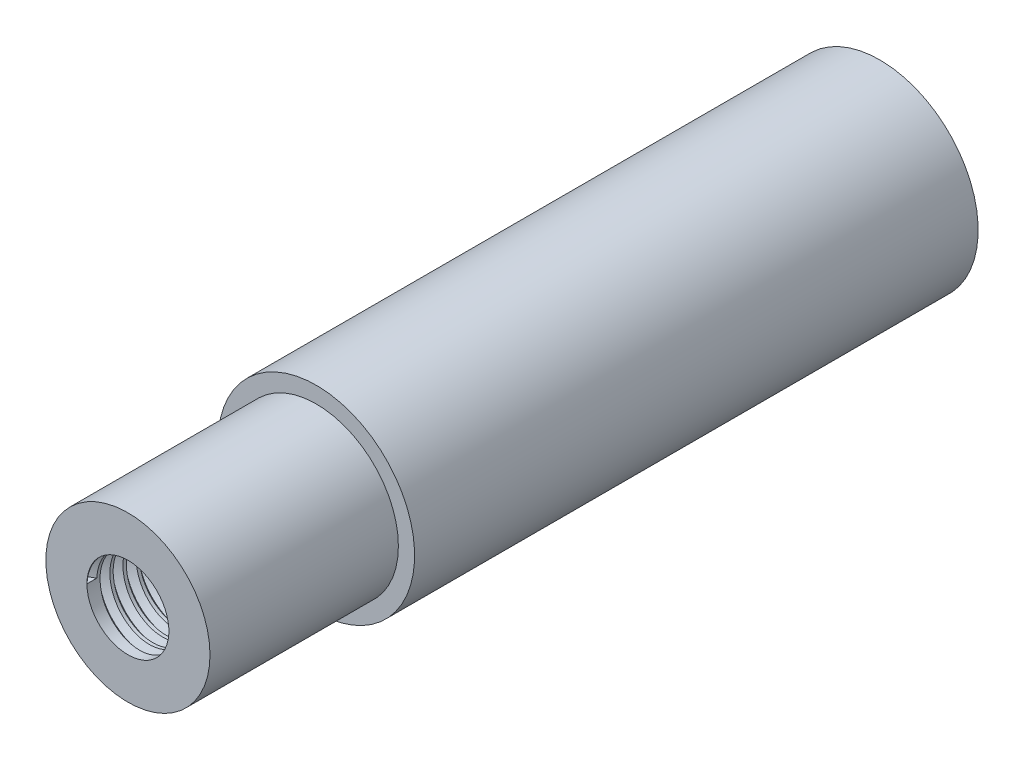
SolidWorks part; units mm, degrees
ref_plane "Front Plane" through (0, 0, 0) normal (0, 0, 1) x (1, 0, 0)
ref_plane "Top Plane" through (0, 0, 0) normal (0, 1, 0) x (1, 0, 0)
ref_plane "Right Plane" through (0, 0, 0) normal (1, 0, 0) x (0, 0, -1)
sketch "Sketch1" plane through (0, 0, 0) normal (0, 0, 1) x (1, 0, 0)
  circle A0 centre (0, 0) radius 6
  circle A1 centre (0, 0) radius 5.01
  dimension "D1" = 12
  dimension "D2" = 10.02
extrude "Boss-Extrude1" add sketch "Sketch1" along normal blind 34.4
sketch "Sketch2" plane through (0, 0, 34.4) normal (0, 0, 1) x (1, 0, 0)
  circle A0 centre (0, 0) radius 5.01 construction
  circle A1 centre (0, 0) radius 5.01
extrude "Boss-Extrude2" add sketch "Sketch2" along normal blind 11.5 separate body
sketch "Sketch3" plane through (0, 0, 45.9) normal (0, 0, 1) x (1, 0, 0)
  circle A0 centre (0, 0) radius 2.5
  dimension "D1" = 5
extrude "Cut-Extrude1" cut sketch "Sketch3" against normal up to surface (11.5 mm away) up to face at (6, 0, 34.4)
thread "Thread1" pitch 0.8 method cut profile "Thread Profile1" start angle 0, offset 0, length 0, pitch 0.8, diameter 5
ref_plane "Plane1" through (-2.5, 0, 45.9) normal (0, -1, 0) x (-1, 0, 0)
sketch "Thread Profile1" plane through (-2.5, 0, 45.9) normal (0, -1, 0) x (-1, 0, 0)
  line L0 (0, 0) -> (0, 0.8) construction
  line L1 (0, 0) -> (0.433, 0.25)
  line L2 (0.433, 0.25) -> (0.433, 0.35)
  line L3 (0.433, 0.35) -> (0, 0.6)
  line L4 (0.433, 0.3) -> (0, 0.3) construction
  line L11 (0, 0) -> (0, 0.6)
  point P2 (0, 0)
  dimension "Pitch" = 0.8
  dimension "Profile_Angle" = 60
  dimension "Profile_Land" = 0.1
  dimension "Profile_Height" = 0.433
sketch "Sketch8" plane through (0, 0, 34.4) normal (0, 0, -1) x (-1, 0, 0)
  circle A0 centre (0, 0) radius 5.01 construction
  circle A1 centre (0, 0) radius 5.01
  circle A2 centre (0, 0) radius 2.933
  dimension "D1" = 5.866
extrude "Boss-Extrude4" add sketch "Sketch8" along normal blind 27
